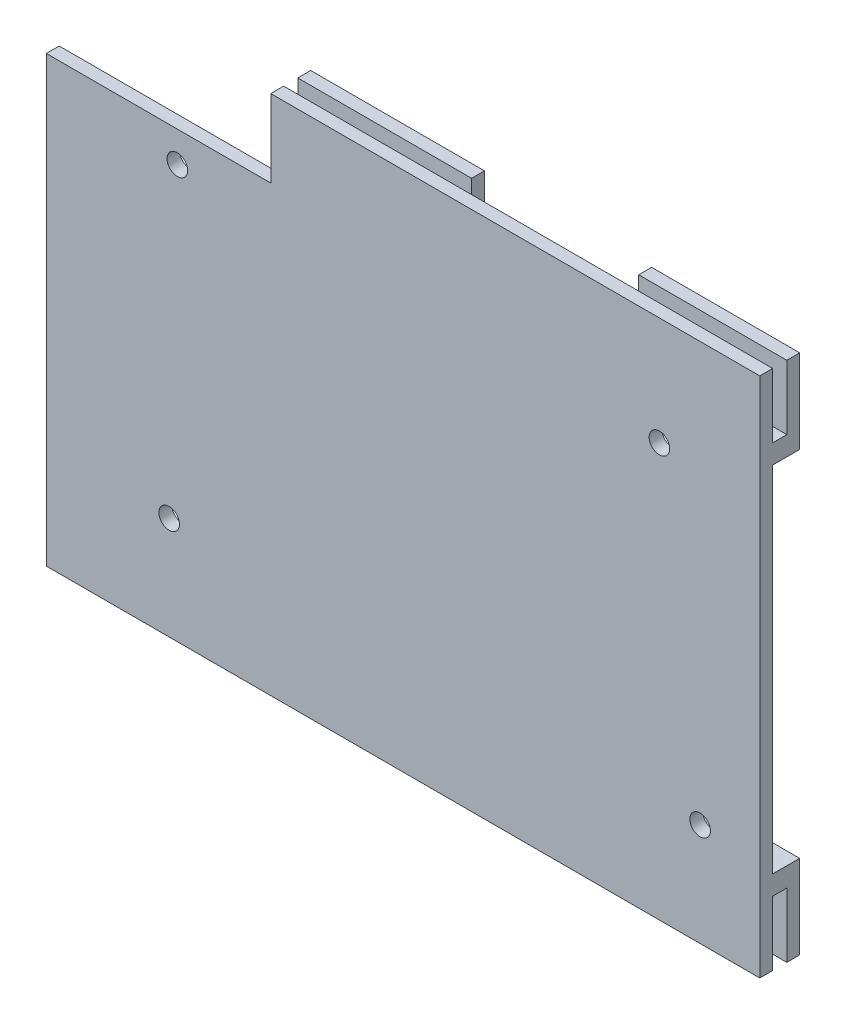
SolidWorks part; units mm, degrees
ref_plane "Front Plane" through (0, 0, 0) normal (0, 0, 1) x (1, 0, 0)
ref_plane "Top Plane" through (0, 0, 0) normal (0, 1, 0) x (1, 0, 0)
ref_plane "Right Plane" through (0, 0, 0) normal (1, 0, 0) x (0, 0, -1)
sketch "Sketch1" plane through (0, 0, 0) normal (0, 0, 1) x (1, 0, 0)
  line L1 (-55, -40) -> (55, -40)
  line L2 (-55, -40) -> (-55, 40)
  line L3 (-55, 40) -> (55, 40)
  line L4 (55, -40) -> (55, 40)
  line L5 (-55, -40) -> (55, 40) construction
  line L6 (-55, 40) -> (55, -40) construction
  point P0 (0, 0)
  dimension "D1" = 110
  dimension "D2" = 80
extrude "Boss-Extrude1" add sketch "Sketch1" along normal blind 2
sketch "Sketch2" plane through (0, 0, 0) normal (0, 0, -1) x (-1, 0, 0)
  circle A0 centre (35.471, 24.1816) radius 1.6
  circle A1 centre (-39.411, 24.1816) radius 1.6
  circle A2 centre (-45.738, -24.0404) radius 1.6
  circle A3 centre (36.741, -24.0404) radius 1.6
  dimension "D1" = 3.2
extrude "Cut-Extrude1" cut sketch "Sketch2" against normal through all
sketch "Sketch3" plane through (0, 0, 2) normal (0, 0, 1) x (1, 0, 0)
  line L1 (-55, 40) -> (-20.9574, 40)
  line L2 (-55, 40) -> (-55, 28.9637)
  line L3 (-55, 28.9637) -> (-20.9574, 28.9637)
  line L4 (-20.9574, 40) -> (-20.9574, 28.9637)
extrude "Cut-Extrude2" cut sketch "Sketch3" against normal through all
sketch "Sketch4" plane through (-55, 0, 0) normal (-1, 0, 0) x (0, 0, 1)
  line L1 (0, -40) -> (2, -40)
  line L2 (0, -40) -> (0, 28.9637)
  line L3 (0, 28.9637) -> (2, 28.9637)
  line L4 (2, -40) -> (2, 28.9637)
extrude "Boss-Extrude2" add sketch "Sketch4" along normal blind 3
sketch "Sketch5" plane through (0, 40, 0) normal (0, 1, 0) x (1, 0, 0)
  line L1 (-20.9574, -2) -> (55, -2)
  line L2 (-20.9574, -2) -> (-20.9574, 0)
  line L3 (-20.9574, 0) -> (55, 0)
  line L4 (55, -2) -> (55, 0)
extrude "Boss-Extrude3" add sketch "Sketch5" along normal blind 1
sketch "Sketch6" plane through (0, 0, 0) normal (0, 0, -1) x (-1, 0, 0)
  line L0 (-55, 0.5) -> (58, 0.5) construction
  line L1 (-55, -40) -> (-55, 41) construction
  line L2 (58, 28.9637) -> (58, -40) construction
  line L4 (-55, 28) -> (58, 28)
  line L5 (-55, 28) -> (-55, 31)
  line L6 (-55, 31) -> (58, 31)
  line L7 (58, 28) -> (58, 31)
  line L8 (58, -27) -> (58, -30)
  line L9 (-55, -30) -> (58, -30)
  line L10 (-55, -27) -> (-55, -30)
  line L11 (-55, -27) -> (58, -27)
  line L12 (-55, 41) -> (20.9574, 41) construction
  dimension "D1" = 10
  dimension "D2" = 3
extrude "Boss-Extrude4" add sketch "Sketch6" along normal blind 2.2
sketch "Sketch7" plane through (0, 0, -2.2) normal (0, 0, -1) x (-1, 0, 0)
  line L1 (-55, 28) -> (58, 28)
  line L2 (-55, 28) -> (-55, 41)
  line L3 (-55, 41) -> (58, 41)
  line L4 (58, 28) -> (58, 41)
  line L5 (-55, 41) -> (20.9574, 41) construction
  line L6 (58, 31) -> (58, 28.9637) construction
  line L7 (-55, 0.5) -> (58, 0.5) construction
  line L8 (-55, -27) -> (-55, 28) construction
  line L9 (58, 28) -> (58, -27) construction
  line L10 (58, -27) -> (58, -40)
  line L11 (-55, -40) -> (58, -40)
  line L12 (-55, -27) -> (-55, -40)
  line L13 (-55, -27) -> (58, -27)
extrude "Boss-Extrude6" add sketch "Sketch7" along normal blind 2
sketch "Sketch10" plane through (0, 0, -2.2) normal (0, 0, 1) x (1, 0, 0)
  line L0 (-58, -40) -> (55, -40) construction
  line L1 (-58, 41) -> (-20.96, 41)
  line L2 (-58, 41) -> (-58, -40)
  line L3 (-58, -40) -> (-20.96, -40)
  line L4 (-20.96, 41) -> (-20.96, -40)
  dimension "D1" = 37.04
extrude "Cut-Extrude5" cut sketch "Sketch10" against normal through all
extrude "Cut-Extrude6" cut sketch "Sketch10<2>" along normal up to surface (2.2 mm away) up to face at (17.0213, 36, 0)
sketch "Sketch10<2>" plane through (0, 0, -2.2) normal (0, 0, 1) x (1, 0, 0) same geometry as "Sketch10"
sketch "Sketch11" plane through (-58, 0, 0) normal (-1, 0, 0) x (0, 0, 1)
  line L1 (0, -40) -> (2, -40)
  line L2 (0, -40) -> (0, 28.9637)
  line L3 (0, 28.9637) -> (2, 28.9637)
  line L4 (2, -40) -> (2, 28.9637)
extrude "Boss-Extrude7" [suppressed] add sketch "Sketch11" along normal blind 3
sketch "Sketch12" plane through (0, 0, -4.2) normal (0, 0, -1) x (-1, 0, 0)
  line L0 (20.96, 41) -> (-55, 41) construction
  line L1 (-32, 41) -> (-6.04, 41)
  line L2 (-32, 41) -> (-32, -40)
  line L3 (-32, -40) -> (-6.04, -40)
  line L4 (-6.04, 41) -> (-6.04, -40)
  line L5 (-55, -40) -> (20.96, -40) construction
  line L7 (-55, -27) -> (-55, 28) construction
  line L8 (20.96, 28) -> (20.96, 41) construction
  dimension "D1" = 23
  dimension "D2" = 27
extrude "Cut-Extrude7" cut sketch "Sketch12" against normal up to surface (4.2 mm away) up to face at (17.0213, 36, 0)
sketch "Sketch13" plane through (0, 0, 0) normal (0, 0, -1) x (-1, 0, 0)
  line L0 (58, -40) -> (-55, -40) construction
  line L1 (60.1765, 97.9273) -> (55.8235, 97.9273)
  line L2 (60.1765, 97.9273) -> (60.1765, -40)
  line L3 (60.1765, -40) -> (55.8235, -40)
  line L4 (55.8235, 97.9273) -> (55.8235, -40)
  line L5 (60.1765, 97.9273) -> (55.8235, -40) construction
  line L6 (60.1765, -40) -> (55.8235, 97.9273) construction
  point P0 (58, 28.9637)
extrude "Cut-Extrude8" cut sketch "Sketch13" against normal through all
